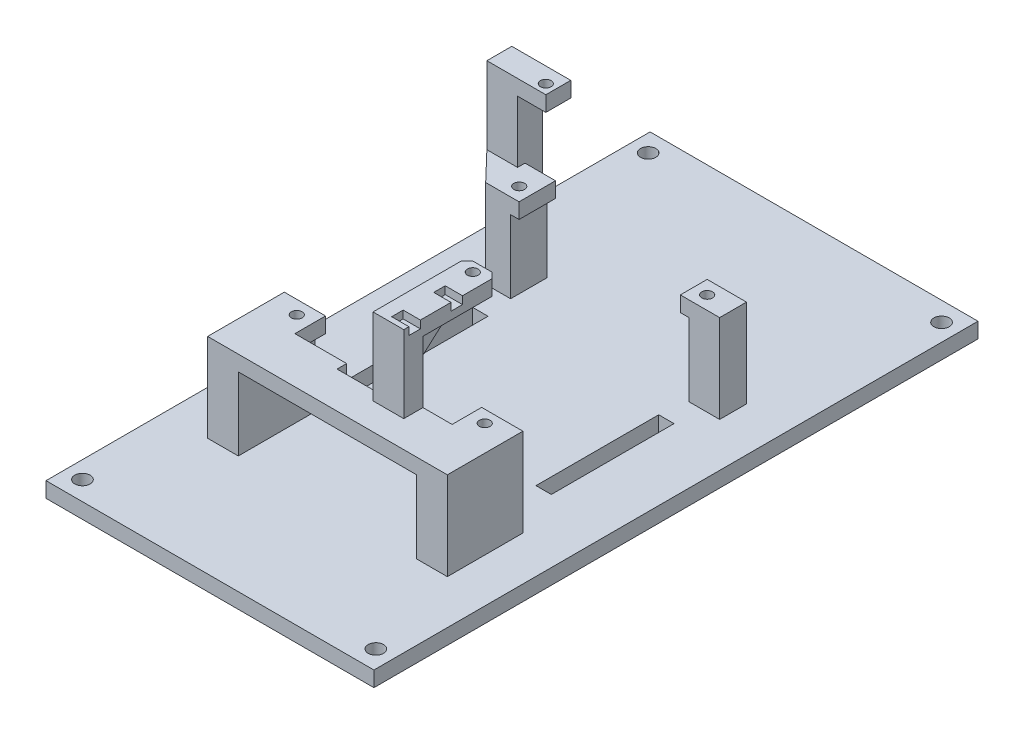
SolidWorks part; units mm, degrees
ref_plane "Front Plane" through (0, 0, 0) normal (0, 0, 1) x (1, 0, 0)
ref_plane "Top Plane" through (0, 0, 0) normal (0, 1, 0) x (1, 0, 0)
ref_plane "Right Plane" through (0, 0, 0) normal (1, 0, 0) x (0, 0, -1)
sketch "Sketch1" plane through (0, 0, 0) normal (0, 1, 0) x (1, 0, 0)
  line L1 (-42.75, 78.75) -> (42.75, 78.75)
  line L2 (-42.75, 78.75) -> (-42.75, -78.75)
  line L3 (-42.75, -78.75) -> (42.75, -78.75)
  line L4 (42.75, 78.75) -> (42.75, -78.75)
  line L5 (-42.75, 78.75) -> (42.75, -78.75) construction
  line L6 (-42.75, -78.75) -> (42.75, 78.75) construction
  point P0 (0, 0)
  dimension "D1" = 157.5
  dimension "D2" = 85.5
extrude "Boss-Extrude1" add sketch "Sketch1" along normal blind 4
sketch "Sketch2" plane through (0, 4, 0) normal (0, 1, 0) x (1, 0, 0)
  line L0 (-42.75, -78.75) -> (42.75, -78.75) construction
  line L1 (42.75, -78.75) -> (42.75, 78.75) construction
  line L2 (0, 0) -> (50000, 0) construction
  line L3 (0, 0) -> (0, -50000) construction
  circle A0 centre (38.25, -73.75) radius 2
  circle A1 centre (38.25, 73.75) radius 2
  circle A2 centre (-38.25, -73.75) radius 2
  circle A3 centre (-38.25, 73.75) radius 2
  dimension "D1" = 4
  dimension "D2" = 5
  dimension "D3" = 4.5
extrude "Cut-Extrude1" cut sketch "Sketch2" against normal up to next
sketch "Sketch5" plane through (0, 4, 0) normal (0, 1, 0) x (1, 0, 0)
  line L0 (-24.5, 26.3886) -> (-24.5, -31.6114) construction
  line L1 (-24.5, -31.6114) -> (24.5, -31.6114) construction
  line L2 (24.5, -31.6114) -> (24.5, 26.3886) construction
  line L3 (24.5, 26.3886) -> (-24.5, 26.3886) construction
  line L4 (0, 49.8886) -> (0, -35.1114) construction
  line L5 (-22.25, 67.25) -> (22.25, 67.25) construction
  line L6 (-22.25, 67.25) -> (-22.25, -67.25) construction
  line L7 (-22.25, -67.25) -> (22.25, -67.25) construction
  line L8 (22.25, 67.25) -> (22.25, -67.25) construction
  line L9 (-22.25, 67.25) -> (22.25, -67.25) construction
  line L10 (-22.25, -67.25) -> (22.25, 67.25) construction
  line L11 (-28, 49.8886) -> (28, 49.8886) construction
  line L12 (-28, 49.8886) -> (-28, -35.1114) construction
  line L13 (-28, -35.1114) -> (28, -35.1114) construction
  line L14 (28, 49.8886) -> (28, -35.1114) construction
  line L15 (24.5, 26.3886) -> (23.25, 26.3886) construction
  line L16 (-37, 36.9499) -> (-29, 36.9499)
  line L18 (-29.75, 22.8886) -> (-23.25, 22.8886)
  line L19 (-23.25, 32.3886) -> (-23.25, 22.8886)
  line L20 (23.25, 29.8886) -> (31.25, 29.8886)
  line L21 (23.25, 29.8886) -> (23.25, 22.8886)
  line L22 (23.25, 22.8886) -> (31.25, 22.8886)
  line L23 (31.25, 29.8886) -> (31.25, 22.8886)
  line L24 (-23.25, -48.1114) -> (23.25, -48.1114) construction
  line L25 (-31.25, -28.1114) -> (-23.25, -28.1114)
  line L26 (-31.25, -28.1114) -> (-31.25, -48.1114)
  line L27 (-31.25, -48.1114) -> (-23.25, -48.1114)
  line L28 (-23.25, -28.1114) -> (-23.25, -48.1114)
  line L29 (23.25, -28.4114) -> (31.25, -28.4114)
  line L30 (23.25, -28.4114) -> (23.25, -48.1114)
  line L31 (23.25, -48.1114) -> (31.25, -48.1114)
  line L32 (31.25, -28.4114) -> (31.25, -48.1114)
  line L33 (22.25, -16) -> (26.25, -16)
  line L34 (-22.25, -16) -> (-26.25, -16)
  line L35 (-22.25, -16) -> (-22.25, 16)
  line L36 (-22.25, 16) -> (-26.25, 16)
  line L37 (-26.25, -16) -> (-26.25, 16)
  line L38 (22.25, -16) -> (22.25, 16)
  line L39 (26.25, -16) -> (26.25, 16)
  line L40 (22.25, 16) -> (26.25, 16)
  line L41 (-23.25, 32.3886) -> (-29, 32.3886)
  line L42 (-29, 32.3886) -> (-29, 36.9499)
  line L43 (-37, 36.9499) -> (-37, 30.4499)
  line L44 (-37, 30.4499) -> (-29.75, 22.8886)
  circle A0 centre (-24.5, 26.3886) radius 1.4
  circle A1 centre (-24.13, 32.9499) radius 1.4
  circle A2 centre (8.89, -19.1201) radius 1.4
  circle A3 centre (24.5, -31.6114) radius 1.4
  circle A4 centre (24.5, 26.3886) radius 1.4
  circle A5 centre (-24.5, -31.6114) radius 1.4
  point P9 (0, 0)
  point P32 (23.25, 26.3886)
  point P46 (-22.25, 0)
  dimension "D1" = 24.5
  dimension "D2" = 26.3886
  dimension "D3" = 32.9499
  dimension "D4" = 24.13
  dimension "D5" = 2.8
  dimension "D6" = 33.02
  dimension "D7" = 52.07
  dimension "D8" = 49
  dimension "D9" = 58
  dimension "D18" = 4
  dimension "D21" = 3.5
  dimension "D24" = 3.5
  dimension "D10" = 44.5
  dimension "D11" = 134.5
  dimension "D12" = 56
  dimension "D13" = 85
  dimension "D14" = 28
  dimension "D15" = 3.5
  dimension "D16" = 1
  dimension "D17" = 3.5
  dimension "D19" = 6.5
  dimension "D20" = 1
  dimension "D22" = 8
  dimension "D23" = 1
  dimension "D25" = 1
  dimension "D26" = 3.2
  dimension "D27" = 8
  dimension "D28" = 8
  dimension "D29" = 20
  dimension "D30" = 32
  dimension "D31" = 4
  dimension "D32" = 6
  dimension "D33" = 1
  dimension "D34" = 8
  dimension "D35" = 6.5
extrude "Cut-Extrude3" cut sketch "Sketch5" against normal up to next contours L37 L34 L35 L36 | L39 L40 L38 L33 region at (-24.25, 4, 0)
extrude "Boss-Extrude3" add sketch "Sketch5<3>" along normal blind 23 contours L32 L29 L30 L31 | L28 L25 L26 L27 | L23 L20 L21 L22 | L43 L44 L18 L19 L41 L42 L16 | L28 A5 | L30 A3 | L21 A4 | L19 A0 | L41 A1 L19 region at (-30.3132, 4, -30.0503) region at (-24.2191, 4, -32.0291) region at (-24.5277, 4, -26.3886) region at (27.5785, 4, -26.3886) region at (24.5277, 4, -26.3886) region at (-27.3566, 4, 38.366) region at (-24.5277, 4, 31.6114) region at (27.3583, 4, 38.526) region at (24.5277, 4, 31.6114)
sketch "Sketch5<3>" plane through (0, 4, 0) normal (0, 1, 0) x (1, 0, 0) same geometry as "Sketch5"
sketch "Sketch6" plane through (-23.25, 0, 0) normal (1, 0, 0) x (0, 0, -1)
  line L0 (-28.1114, 27) -> (-28.1114, 4) construction
  line L1 (-48.1114, 27) -> (-28.1114, 27)
  line L2 (-48.1114, 27) -> (-48.1114, 23)
  line L3 (-48.1114, 23) -> (-28.1114, 23)
  line L4 (-28.1114, 27) -> (-28.1114, 23)
  line L5 (-28.1114, 4) -> (-48.1114, 4) construction
  dimension "D1" = 19
extrude "Boss-Extrude5" add sketch "Sketch6" along normal up to surface (46.5 mm away) up to face at (23.25, 15.5, 38.2614)
sketch "Sketch7" plane through (0, 27, 0) normal (0, 1, 0) x (1, 0, 0)
  line L0 (-31.25, -28.1114) -> (23.25, -28.1114) construction
  line L1 (-20.5, -28.1114) -> (23.25, -28.1114)
  line L2 (-20.5, -28.1114) -> (-20.5, -36.1114)
  line L3 (-20.5, -36.1114) -> (20.5, -36.1114)
  line L4 (20.5, -28.4114) -> (20.5, -36.1114)
  line L5 (23.25, -28.4114) -> (20.5, -28.4114)
  line L6 (23.25, -28.1114) -> (23.25, -28.4114)
  line L7 (-31.25, -28.1114) -> (-31.25, -48.1114) construction
  line L8 (31.25, -28.4114) -> (31.25, -48.1114) construction
  dimension "D1" = 10.75
  dimension "D2" = 10.75
  dimension "D3" = 8
extrude "Cut-Extrude4" cut sketch "Sketch7" against normal up to next
sketch "Sketch8" plane through (23.25, 0, 0) normal (-1, 0, 0) x (0, 0, 1)
  line L0 (-22.8886, 27) -> (-22.8886, 4) construction
  line L1 (-29.8886, 27) -> (-22.8886, 27)
  line L2 (-29.8886, 27) -> (-29.8886, 23)
  line L3 (-29.8886, 23) -> (-22.8886, 23)
  line L4 (-22.8886, 27) -> (-22.8886, 23)
  line L5 (-29.8886, 4) -> (-22.8886, 4) construction
  dimension "D1" = 19
extrude "Boss-Extrude6" add sketch "Sketch8" along normal blind 2.25
sketch "Sketch9" plane through (-23.25, 0, 0) normal (1, 0, 0) x (0, 0, -1)
  line L0 (32.3886, 27) -> (32.3886, 4) construction
  line L1 (22.8886, 27) -> (32.3886, 27)
  line L2 (22.8886, 27) -> (22.8886, 23)
  line L3 (22.8886, 23) -> (32.3886, 23)
  line L4 (32.3886, 27) -> (32.3886, 23)
  line L5 (32.3886, 4) -> (22.8886, 4) construction
  dimension "D1" = 19
extrude "Boss-Extrude7" add sketch "Sketch9" along normal blind 2.2
extrude "Cut-Extrude5" cut sketch "Sketch5<5>" against normal blind 3.5 from surface contours A0 | A4 | A3 | A5 starting at face at (0, 27, 35.1864)
sketch "Sketch5<5>" plane through (0, 4, 0) normal (0, 1, 0) x (1, 0, 0) same geometry as "Sketch5"
sketch "Sketch13" plane through (0, 27, 0) normal (0, 1, 0) x (1, 0, 0)
  line L0 (-29, 32.3886) -> (-29, 36.9499) construction
  line L1 (-37, 36.9499) -> (-29, 36.9499)
  line L2 (-37, 36.9499) -> (-37, 30.4499)
  line L3 (-37, 30.4499) -> (-29, 30.4499)
  line L4 (-29, 36.9499) -> (-29, 30.4499)
  line L5 (-20.5, -36.1114) -> (20.5, -36.1114) construction
  line L6 (4.89, -36.1114) -> (12.89, -36.1114)
  line L7 (4.89, -36.1114) -> (4.89, -41.1114)
  line L8 (4.89, -41.1114) -> (12.89, -41.1114)
  line L9 (12.89, -36.1114) -> (12.89, -41.1114)
  line L10 (8.89, -19.1201) -> (8.89, -36.1114) construction
  circle A0 centre (-24.13, 32.9499) radius 1.4 construction
  point P15 (8.89, -36.1114)
  dimension "D1" = 2.5
  dimension "D2" = 5
  dimension "D3" = 8
extrude "Boss-Extrude8" add sketch "Sketch13" along normal blind 20.1
sketch "Sketch14" plane through (-29, 0, 0) normal (1, 0, 0) x (0, 0, -1)
  line L0 (36.9499, 47.1) -> (36.9499, 4) construction
  line L1 (30.4499, 47.1) -> (36.9499, 47.1)
  line L2 (30.4499, 47.1) -> (30.4499, 43.1)
  line L3 (30.4499, 43.1) -> (36.9499, 43.1)
  line L4 (36.9499, 47.1) -> (36.9499, 43.1)
  dimension "D1" = 4
extrude "Boss-Extrude9" add sketch "Sketch14" along normal blind 7.37
sketch "Sketch15" plane through (0, 0, 36.1114) normal (0, 0, -1) x (-1, 0, 0)
  line L0 (-4.89, 47.1) -> (-4.89, 27) construction
  line L1 (-12.89, 47.1) -> (-4.89, 47.1)
  line L2 (-12.89, 47.1) -> (-12.89, 43.1)
  line L3 (-12.89, 43.1) -> (-4.89, 43.1)
  line L4 (-4.89, 47.1) -> (-4.89, 43.1)
  dimension "D1" = 4
extrude "Boss-Extrude10" add sketch "Sketch15" along normal blind 19.4913
extrude "Cut-Extrude6" cut sketch "Sketch5<6>" against normal up to next from surface contours A2 | A1 starting at face at (-29.315, 47.1, -33.6999)
sketch "Sketch5<6>" plane through (0, 4, 0) normal (0, 1, 0) x (1, 0, 0) same geometry as "Sketch5"
sketch "Sketch16" plane through (0, 47.1, 0) normal (0, 1, 0) x (1, 0, 0)
  line L0 (8.89, -19.1201) -> (8.89, -27.2991) construction
  line L1 (8.89, -27.2991) -> (12.89, -27.2991) construction
  line L2 (12.89, -41.1114) -> (12.89, -16.6201) construction
  line L3 (8.39, -28.7991) -> (12.89, -28.7991)
  line L4 (8.39, -25.7991) -> (8.39, -28.7991)
  line L5 (8.39, -25.7991) -> (12.89, -25.7991)
  line L6 (8.39, -39.7721) -> (12.89, -39.7721)
  line L7 (8.89, -28.2991) -> (12.89, -28.2991) construction
  line L8 (8.89, -26.2991) -> (12.89, -26.2991) construction
  line L10 (8.89, -26.2991) -> (8.89, -28.2991) construction
  line L11 (8.89, -27.2991) -> (8.89, -38.2721) construction
  line L12 (8.89, -38.2721) -> (12.89, -38.2721) construction
  line L13 (12.89, -41.1114) -> (12.89, -36.1114) construction
  line L14 (8.89, -39.2721) -> (12.89, -39.2721) construction
  line L15 (8.89, -37.2721) -> (12.89, -37.2721) construction
  line L16 (8.89, -37.2721) -> (8.89, -39.2721) construction
  line L18 (8.39, -36.7721) -> (8.39, -39.7721)
  line L19 (8.39, -36.7721) -> (12.89, -36.7721)
  line L20 (12.89, -25.7991) -> (12.89, -28.7991)
  line L21 (12.89, -36.7721) -> (12.89, -39.7721)
  dimension "D1" = 8.179
  dimension "D2" = 1
  dimension "D4" = 10.973
  dimension "D5" = 1
  dimension "D7" = 0.5
  dimension "D3" = 1
  dimension "D6" = 1
extrude "Cut-Extrude7" cut sketch "Sketch16" against normal blind 2
chamfer "Chamfer1" distance 1.5 angle 45 2 edges at (4.89, 45.1, 16.6201) (12.89, 45.1, 16.6201)
ref_plane "Plane1" through (8.89, 0, 0) normal (-1, 0, 0) x (0, 0, 1)
sketch "Sketch19" plane through (8.89, 0, 0) normal (-1, 0, 0) x (0, 0, 1)
  line L0 (27.1157, 43.1) -> (36.1114, 35.05)
  line L1 (18.1201, 43.1) -> (36.1114, 43.1) construction
  line L2 (36.1114, 43.1) -> (36.1114, 27) construction
  line L3 (27.1157, 43.1) -> (36.1114, 43.1)
  line L4 (36.1114, 43.1) -> (36.1114, 35.05)
extrude "Boss-Extrude11" add sketch "Sketch19" along normal blind 2 and the other way blind 2
sketch "Sketch20" plane through (0, 0, -36.9499) normal (0, 0, -1) x (-1, 0, 0)
  line L1 (37, 4) -> (31.25, 4)
  line L2 (37, 4) -> (37, 10)
  line L3 (37, 10) -> (31.25, 10)
  line L4 (31.25, 4) -> (31.25, 10)
  dimension "D1" = 5.75
  dimension "D2" = 6
extrude "Cut-Extrude8" cut sketch "Sketch20" against normal up to next
chamfer "Chamfer2" distance 5.75 angle 45 1 edges at (-37, 10, -33.6999)
sketch "Sketch21" plane through (0, 0, -36.9499) normal (0, 0, -1) x (-1, 0, 0)
  line L1 (31.25, 10) -> (29, 10)
  line L2 (31.25, 10) -> (31.25, 4)
  line L3 (31.25, 4) -> (29, 4)
  line L4 (29, 10) -> (29, 4)
extrude "Cut-Extrude9" cut sketch "Sketch21" against normal up to surface (4.5613 mm away) up to face at (-24.4333, 18, -32.3886)
chamfer "Chamfer3" distance 5.75 distance2 4.5613 1 edges at (-30.125, 10, -36.9499) first distance on face at (-29.5014, 30.8786, -36.9499)
sketch "Sketch22" plane through (0, 27, 0) normal (0, 1, 0) x (1, 0, 0)
  line L0 (0, -48.1114) -> (0, -36.1114) construction
  line L1 (-31.25, -48.1114) -> (31.25, -48.1114) construction
  line L2 (-20.5, -36.1114) -> (4.89, -36.1114) construction
  line L3 (-7, -36.1114) -> (-7, -38.6114)
  line L4 (-7, -38.6114) -> (7, -38.6114)
  line L5 (7, -38.6114) -> (7, -36.1114)
  line L6 (7, -36.1114) -> (-7, -36.1114)
  point P13 (0, -36.1114)
  dimension "D1" = 14
  dimension "D2" = 2.5
extrude "Cut-Extrude10" cut sketch "Sketch22" against normal blind 2.5
chamfer "Chamfer4" distance 2.5 angle 45 1 edges at (5.945, 27, 36.1114)
